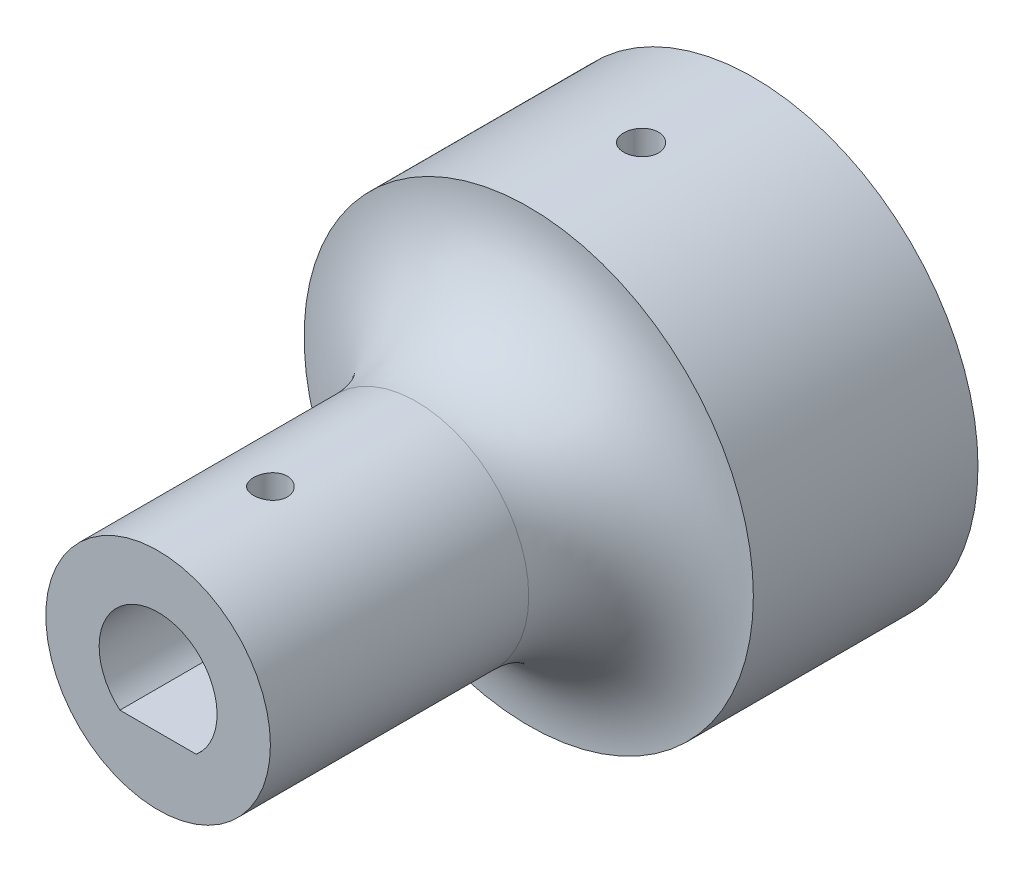
SolidWorks part; units mm, degrees
ref_plane "前视基准面" through (0, 0, 0) normal (0, 0, 1) x (1, 0, 0)
ref_plane "上视基准面" through (0, 0, 0) normal (0, 1, 0) x (1, 0, 0)
ref_plane "右视基准面" through (0, 0, 0) normal (1, 0, 0) x (0, 0, -1)
sketch "草图1" plane through (0, 0, 0) normal (0, 0, 1) x (1, 0, 0)
  line L0 (0, 0) -> (0, 20) construction
  circle A0 centre (0, 0) radius 20
  point P17 (0, 0)
  dimension "D1" = 40
extrude "凸台-拉伸1" add sketch "草图1" along normal blind 20
sketch "草图2" plane through (0, 0, 20) normal (0, 0, 1) x (1, 0, 0)
  circle A0 centre (0, 0) radius 10
  dimension "D1" = 20
extrude "凸台-拉伸2" add sketch "草图2" along normal blind 33
sketch "草图4" plane through (0, 0, 0) normal (0, 0, -1) x (-1, 0, 0)
  line L1 (-10.5, 10.5) -> (10.5, 10.5)
  line L2 (-10.5, 10.5) -> (-10.5, -10.5)
  line L3 (-10.5, -10.5) -> (10.5, -10.5)
  line L4 (10.5, 10.5) -> (10.5, -10.5)
  line L5 (0, -10.5) -> (0, 10.5) construction
  line L6 (-10.5, 0) -> (10.5, 0) construction
  line L7 (-8.5, 8.5) -> (8.5, 8.5)
  line L8 (-8.5, 8.5) -> (-8.5, -8.5)
  line L9 (-8.5, -8.5) -> (8.5, -8.5)
  line L10 (8.5, 8.5) -> (8.5, -8.5)
  line L11 (0, -8.5) -> (0, 8.5) construction
  line L12 (-8.5, 0) -> (8.5, 0) construction
  point P0 (0, 0)
  point P4 (0, 0)
  dimension "D1" = 17
  dimension "D2" = 21
  dimension "D3" = 17
  dimension "D4" = 21
extrude "切除-拉伸3" cut sketch "草图4" against normal blind 15
sketch "草图5" plane through (0, 0, 0) normal (0, 1, 0) x (1, 0, 0)
  line L0 (0, 0) -> (0, -53) construction
  line L1 (-10, -53) -> (10, -53) construction
  line L2 (-10.5, 0) -> (10.5, 0) construction
  circle A1 centre (0, -10) radius 1.55
  dimension "D2" = 3.1
  dimension "D3" = 10
extrude "切除-拉伸4" cut sketch "草图5" against normal through all both and the other way through all
fillet "圆角1" radius 10 1 edges at (10, 0, 20)
sketch "草图8" plane through (0, 0, 53) normal (0, 0, 1) x (1, 0, 0)
  line L1 (-3.4004, -4) -> (3.4004, -4)
  arc A1 (3.4004, -4) -> (-3.4004, -4) centre (0, 0) ccw
  dimension "D1" = 10.5
  dimension "D2" = 4
extrude "切除-拉伸6" cut sketch "草图8" against normal blind 20
sketch "草图9" plane through (0, -4, 0) normal (0, 1, 0) x (1, 0, 0)
  line L0 (0, -53) -> (0, -43) construction
  line L1 (-10, -53) -> (10, -53) construction
  circle A0 centre (0, -43) radius 1.5
  dimension "D2" = 3
  dimension "D1" = 10
extrude "切除-拉伸7" cut sketch "草图9" against normal through all both and the other way through all
